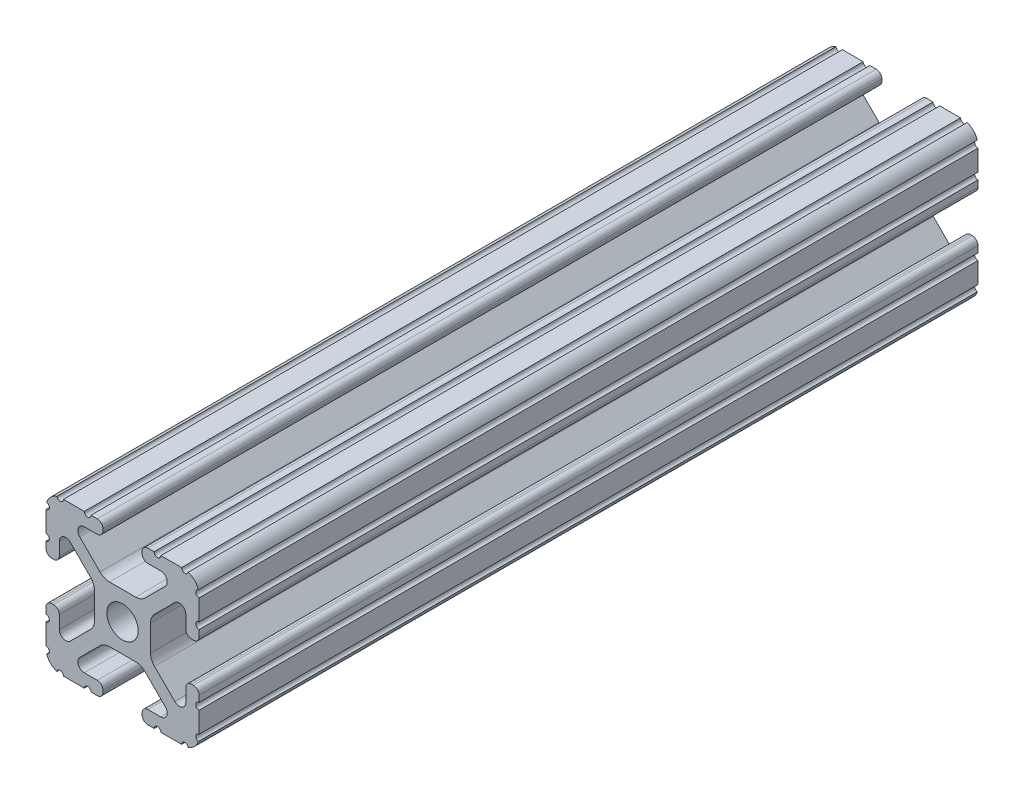
SolidWorks part; units mm, degrees
ref_plane "Front Plane" through (0, 0, 0) normal (0, 0, 1) x (1, 0, 0)
ref_plane "Top Plane" through (0, 0, 0) normal (0, 1, 0) x (1, 0, 0)
ref_plane "Right Plane" through (0, 0, 0) normal (1, 0, 0) x (0, 0, -1)
sketch "Sketch2" plane through (0, 0, 0) normal (0, 0, 1) x (1, 0, 0)
  line L0 (0, 12.7) -> (0, -12.7) construction
  line L1 (-12.7, 0) -> (12.7, 0) construction
  line L2 (3.2512, -12.7) -> (12.7, -12.7)
  line L3 (12.7, -12.7) -> (12.7, -3.2512)
  line L4 (3.2512, -12.7) -> (3.2512, -10.4902)
  line L5 (3.2512, -10.4902) -> (8.9276, -10.4902)
  line L6 (8.9276, -10.4902) -> (3.0856, -4.6482)
  line L7 (0, 0) -> (12.7, -12.7) construction
  line L8 (12.7, -3.2512) -> (10.4902, -3.2512)
  line L9 (10.4902, -3.2512) -> (10.4902, -8.9276)
  line L10 (10.4902, -8.9276) -> (4.6482, -3.0856)
  circle A0 centre (0, 0) radius 2.6035
  arc A1 (6.3485, -10.4902) -> (7.1039, -8.6665) centre (6.3485, -9.4219) ccw construction
  point P8 (0, -4.6482)
  dimension "Center Hole Diameter" = 5.207
  dimension "Rail Height" = 25.4
  dimension "Rail Width" = 25.4
  dimension "T-Slot Width" = 6.5024
  dimension "Slot Inner Width" = 14.8336
  dimension "Thickness" = 2.2098
  dimension "Slot Depth" = 5.842
  dimension "D1" = 2.2098
sketch "Sketch3" plane through (0, 0, 0) normal (1, 0, 0) x (0, 0, -1)
  line L0 (-228.6, -12.7) -> (228.6, -12.7) construction
  line L1 (-205.74, 0) -> (205.74, 0) construction
  dimension "Length" = 457.2
  dimension "D1" = 411.48
sketch "Sketch4" plane through (0, 0, 0) normal (0, 0, 1) x (1, 0, 0)
  line L0 (4.1904, -12.7) -> (10.1173, -12.7)
  line L1 (3.2512, -12.7) -> (12.7, -12.7) construction
  line L2 (3.2512, -12.7) -> (3.2512, -10.4902) construction
  line L3 (3.2512, -10.4902) -> (8.9276, -10.4902) construction
  line L4 (3.2512, -11.4294) -> (3.2512, -11.7608)
  line L5 (4.1904, -10.4902) -> (6.3485, -10.4902)
  line L6 (0, -4.6482) -> (2.164, -4.6482)
  line L7 (8.9276, -10.4902) -> (3.0856, -4.6482) construction
  line L8 (3.7373, -5.2999) -> (7.1039, -8.6665)
  line L9 (12.7, -12.7) -> (12.7, -3.2512) construction
  line L10 (10.4902, -8.9276) -> (4.6482, -3.0856) construction
  line L11 (10.4902, -3.2512) -> (10.4902, -8.9276) construction
  line L12 (10.4902, -6.3485) -> (10.4902, -4.1904)
  line L13 (12.7, -3.2512) -> (10.4902, -3.2512) construction
  line L14 (11.4294, -3.2512) -> (11.7608, -3.2512)
  line L15 (12.7, -4.1904) -> (12.7, -10.1173)
  line L16 (8.6665, -7.1039) -> (5.2999, -3.7373)
  line L17 (4.6482, 0) -> (4.6482, -2.164)
  line L18 (-12.7, 0) -> (12.7, 0) construction
  line L19 (0, -4.6482) -> (0, -2.6035)
  line L20 (0, 12.7) -> (0, -12.7) construction
  line L21 (4.6482, 0) -> (2.6035, 0)
  arc A0 (3.2512, -11.7608) -> (4.1904, -12.7) centre (4.1904, -11.7608) ccw
  arc A2 (3.2512, -11.4294) -> (4.1904, -10.4902) centre (4.1904, -11.4294) cw
  arc A3 (6.3485, -10.4902) -> (7.1039, -8.6665) centre (6.3485, -9.4219) ccw
  arc A4 (2.164, -4.6482) -> (3.7373, -5.2999) centre (2.164, -6.8732) cw
  arc A5 (10.1173, -12.7) -> (12.7, -10.1173) centre (10.1173, -10.1173) ccw
  arc A6 (8.6665, -7.1039) -> (10.4902, -6.3485) centre (9.4219, -6.3485) ccw
  arc A7 (10.4902, -4.1904) -> (11.4294, -3.2512) centre (11.4294, -4.1904) cw
  arc A8 (11.7608, -3.2512) -> (12.7, -4.1904) centre (11.7608, -4.1904) cw
  arc A9 (5.2999, -3.7373) -> (4.6482, -2.164) centre (6.8732, -2.164) cw
  circle A10 centre (0, 0) radius 2.6035 construction
  arc A11 (0, -2.6035) -> (2.6035, 0) centre (0, 0) ccw
  dimension "D1" = 2.5827
  dimension "D2" = 2.225
  dimension "D3" = 0.9392
extrude "Boss-Extrude1" add sketch "Sketch4" along normal mid plane 129.24
sketch "Sketch5" plane through (0, 0, 0) normal (0, 0, 1) x (1, 0, 0)
  line L0 (3.2512, -12.7) -> (12.7, -12.7) construction
  line L1 (4.1904, -10.4902) -> (6.3485, -10.4902) construction
  line L3 (0, 0) -> (12.7, -12.7) construction
  line L4 (6.3485, -10.4902) -> (6.3485, -12.7) construction
  line L5 (8.9276, -10.4902) -> (3.0856, -4.6482) construction
  circle A0 centre (10.3562, -12.7) radius 0.5524
  circle A1 centre (5.796, -12.7) radius 0.5524
  circle A2 centre (12.7, -10.3562) radius 0.5524
  circle A3 centre (12.7, -5.796) radius 0.5524
  point P10 (5.2694, -10.4902)
  point P12 (9.4219, -6.3485)
  dimension "D1" = 1.1049
extrude "Cut-Extrude1" cut sketch "Sketch5" against normal through all both and the other way through all
mirror "Mirror1" about plane through (0, 0, 0) normal (1, 0, 0) of bodies 137 134
mirror "Mirror2" about plane through (0, 0, 0) normal (0, 1, 0) of bodies 135
equation "\"D1@Boss-Extrude1\"=\"Length@Sketch3\""
equation "\"D1@Sketch2\"=\"Thickness@Sketch2\""
equation "\"D2@Sketch4\"=\"Slot Inner Width@Sketch2\"*0.15"
equation "\"D1@Sketch4\"=\"D3@Sketch4\"*2.75"
equation "\"D3@Sketch4\"=\"Thickness@Sketch2\"*0.425"
equation "\"D1@Sketch5\"=\"Thickness@Sketch2\"*0.5"
equation "\"D1@Sketch3\"=\"Length@Sketch3\"*0.9"
